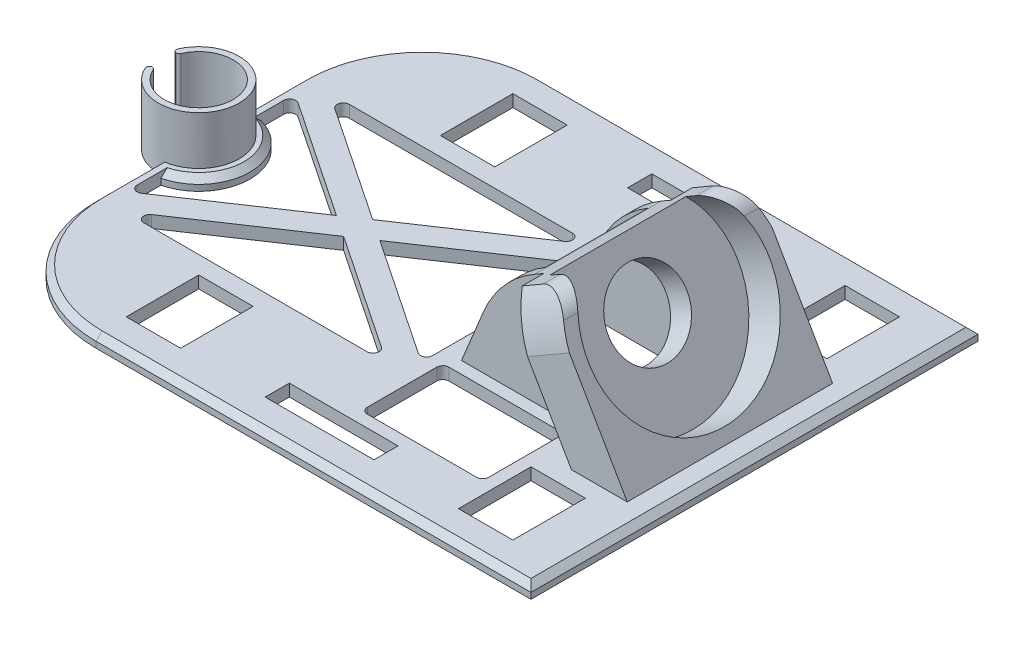
SolidWorks part; units mm, degrees
ref_plane "Plano frontal" through (0, 0, 0) normal (0, 0, 1) x (1, 0, 0)
ref_plane "Plano superior" through (0, 0, 0) normal (0, 1, 0) x (1, 0, 0)
ref_plane "Plano direito" through (0, 0, 0) normal (1, 0, 0) x (0, 0, -1)
sketch "Esboço1" plane through (0, 0, 0) normal (0, 1, 0) x (1, 0, 0)
  line L1 (-23, 18.5) -> (23, 18.5)
  line L2 (-23, 18.5) -> (-23, -18.5)
  line L3 (-23, -18.5) -> (23, -18.5)
  line L4 (23, 18.5) -> (23, -18.5)
  line L5 (-23, 18.5) -> (23, -18.5) construction
  line L6 (-23, -18.5) -> (23, 18.5) construction
  point P0 (0, 0)
  dimension "D1" = 46
  dimension "D2" = 37
extrude "Ressalto-extrusão1" add sketch "Esboço1" along normal blind 1
sketch "Esboço2" plane through (0, 1, 0) normal (0, 1, 0) x (1, 0, 0)
  line L0 (-23, 18.5) -> (-23, -18.5) construction
  line L1 (-13, -16) -> (-8.5, -16)
  line L2 (-13, -16) -> (-13, -10)
  line L3 (-13, -10) -> (-8.5, -10)
  line L4 (-8.5, -16) -> (-8.5, -10)
  line L9 (-1.5, -16) -> (7.5, -16)
  line L10 (-1.5, -16) -> (-1.5, -14)
  line L11 (-1.5, -14) -> (7.5, -14)
  line L12 (7.5, -16) -> (7.5, -14)
  line L13 (14.5, -16) -> (19, -16)
  line L14 (14.5, -16) -> (14.5, -10)
  line L15 (14.5, -10) -> (19, -10)
  line L16 (19, -16) -> (19, -10)
  line L17 (-13, 16) -> (-8.5, 16)
  line L18 (-13, 16) -> (-13, 10)
  line L19 (-13, 10) -> (-8.5, 10)
  line L20 (-8.5, 16) -> (-8.5, 10)
  line L25 (-1.5, 16) -> (7.5, 16)
  line L26 (-1.5, 16) -> (-1.5, 14)
  line L27 (-1.5, 14) -> (7.5, 14)
  line L28 (7.5, 16) -> (7.5, 14)
  line L29 (14.5, 16) -> (19, 16)
  line L30 (14.5, 16) -> (14.5, 10)
  line L31 (14.5, 10) -> (19, 10)
  line L32 (19, 16) -> (19, 10)
  dimension "D1" = 4.5
  dimension "D2" = 10
  dimension "D3" = 28
  dimension "D4" = 14
  dimension "D5" = 2
  dimension "D6" = 2
  dimension "D7" = 6
  dimension "D8" = 6
  dimension "D9" = 7
  dimension "D10" = 9
  dimension "D13" = 7
  dimension "D14" = 4.5
extrude "Corte-extrusão1" cut sketch "Esboço2" against normal blind 3
sketch "Esboço3" plane through (0, 1, 0) normal (0, 1, 0) x (1, 0, 0)
  line L0 (23, -18.5) -> (23, 18.5) construction
  line L1 (4, 8.4674) -> (21, 8.4674)
  line L2 (4, 8.4674) -> (4, -8.5326)
  line L3 (4, -8.5326) -> (21, -8.5326)
  line L4 (21, 8.4674) -> (21, -8.5326)
  line L5 (4, 8.4674) -> (21, -8.5326) construction
  line L6 (4, -8.5326) -> (21, 8.4674) construction
  point P0 (12.5, -0.0326)
  dimension "D1" = 17
  dimension "D2" = 17
  dimension "D3" = 2
extrude "Ressalto-extrusão2" add sketch "Esboço3" along normal blind 15
chamfer "Chanfro1" distance 15 angle 30 1 edges at (21, 16, 0.0326) first distance on face at (21, 8.5, 0.0326)
sketch "Esboço4" plane through (16.183, 9.3433, 0) normal (0.866, 0.5, 0) x (0, 0, -1)
  line L0 (-8.5326, -9.634) -> (8.4674, -9.634) construction
  circle A0 centre (0, -1.134) radius 7.5
  dimension "D1" = 15
  dimension "D2" = 8.5
extrude "Corte-extrusão2" cut sketch "Esboço4" against normal blind 3
sketch "Esboço5" plane through (13.5849, 7.8433, 0) normal (0.866, 0.5, 0) x (0, 0, -1)
  circle A0 centre (0, -1.134) radius 3.25
  dimension "D1" = 6.5
extrude "Corte-extrusão3" cut sketch "Esboço5" against normal blind 2
sketch "Esboço6" plane through (11.8529, 6.8433, 0) normal (0.866, 0.5, 0) x (0, 0, -1)
  line L1 (-4.25, 5.167) -> (4.25, 5.167)
  line L2 (-4.25, 5.167) -> (-4.25, -7.4349)
  line L3 (-4.25, -7.4349) -> (4.25, -7.4349)
  line L4 (4.25, 5.167) -> (4.25, -7.4349)
  line L5 (-4.25, 5.167) -> (4.25, -7.4349) construction
  line L6 (-4.25, -7.4349) -> (4.25, 5.167) construction
  point P0 (0, -1.134)
  dimension "D1" = 8.5
extrude "Corte-extrusão4" cut sketch "Esboço6" against normal blind 10
sketch "Esboço7" plane through (16.183, 9.3433, 0) normal (0.866, 0.5, 0) x (0, 0, -1)
  line L1 (-8.5326, 7.6865) -> (8.4674, 7.6865)
  line L2 (-8.5326, 7.6865) -> (-8.5326, 11.8564)
  line L3 (-8.5326, 11.8564) -> (8.4674, 11.8564)
  line L4 (8.4674, 7.6865) -> (8.4674, 11.8564)
extrude "Corte-extrusão5" cut sketch "Esboço7" against normal blind 10
sketch "Esboço10" plane through (-2.5835, 4.4747, 0) normal (0.5, -0.866, 0) x (0.866, 0.5, 0)
  line L1 (7.602, 4.25) -> (13.6865, 4.25)
  line L2 (7.602, 4.25) -> (7.602, -4.25)
  line L3 (7.602, -4.25) -> (13.6865, -4.25)
  line L4 (13.6865, 4.25) -> (13.6865, -4.25)
extrude "Corte-extrusão6" cut sketch "Esboço10" along normal blind 20
sketch "Esboço11" plane through (4, 0, 0) normal (-1, 0, 0) x (0, 0, 1)
  line L1 (-4.25, 11.318) -> (4.25, 11.318)
  line L2 (-4.25, 11.318) -> (-4.25, 8.2757)
  line L3 (-4.25, 8.2757) -> (4.25, 8.2757)
  line L4 (4.25, 11.318) -> (4.25, 8.2757)
extrude "Corte-extrusão7" cut sketch "Esboço11" against normal up to surface (5.2694 mm away) up to face at (12.5366, 5.659, 0)
sketch "Esboço12" plane through (-3.8433, 6.6567, 0) normal (-0.5, 0.866, 0) x (0.866, 0.5, 0)
  line L1 (13.6865, -4.25) -> (9.3225, -4.25)
  line L2 (13.6865, -4.25) -> (13.6865, 4.25)
  line L3 (13.6865, 4.25) -> (9.3225, 4.25)
  line L4 (9.3225, -4.25) -> (9.3225, 4.25)
extrude "Corte-extrusão8" cut sketch "Esboço12" against normal blind 8
sketch "Esboço17" plane through (0, 1, 0) normal (0, 1, 0) x (1, 0, 0)
  line L0 (-23, 18.5) -> (-23, -18.5) construction
  circle A0 centre (-23, 0) radius 3.35
  dimension "D1" = 6.7
extrude "Ressalto-extrusão4" add sketch "Esboço17" along normal blind 5 from offset 1 offset against normal yes
sketch "Esboço18" plane through (0, 5, 0) normal (0, 1, 0) x (1, 0, 0)
  circle A0 centre (-23, 0) radius 2.85
  dimension "D1" = 5.7
extrude "Corte-extrusão11" cut sketch "Esboço18" against normal blind 10
sketch "Esboço19" plane through (-23, 0, 0) normal (-1, 0, 0) x (0, 0, 1)
  line L0 (-0.988, 10.7689) -> (-0.988, -0.812)
  line L1 (-0.988, 10.7689) -> (1.012, 10.7689)
  line L2 (-0.988, -0.812) -> (1.012, -0.812)
  line L3 (1.012, 10.7689) -> (1.012, -0.812)
  line L4 (-0.988, 10.7689) -> (1.012, -0.812) construction
  line L5 (-0.988, -0.812) -> (1.012, 10.7689) construction
  point P0 (-0.988, -0.812)
  point P1 (0.012, 4.9785)
  dimension "D1" = 2
extrude "Corte-extrusão12" cut sketch "Esboço19" along normal blind 6
sketch "Esboço25" plane through (16.183, 9.3433, 0) normal (0.866, 0.5, 0) x (0, 0, -1)
  line L0 (-8.6, -1.134) -> (-8.6651, 8.1195)
  line L1 (-8.6651, 8.1195) -> (8.6, 8.1195)
  line L2 (8.6, 8.1195) -> (8.6, -1.134)
  arc A0 (8.6, -1.134) -> (-8.6, -1.134) centre (0, -1.134) ccw
  dimension "D1" = 8.6
extrude "Corte-extrusão17" cut sketch "Esboço25" against normal up to surface (14.7224 mm away) up to face at (8.1699, 1, 0.0163)
sketch "Esboço26" plane through (0, 0, 8.5326) normal (0, 0, 1) x (1, 0, 0)
  line L0 (4, 1) -> (8.6816, 12.336)
  line L1 (8.6816, 12.336) -> (1.8349, 10.7026)
  line L2 (1.8349, 10.7026) -> (4, 1)
extrude "Corte-extrusão18" cut sketch "Esboço26" against normal blind 34
ref_plane "Plano1" through (-3.1712, 5.4928, 0) normal (0.5, -0.866, 0) x (-0.866, -0.5, 0)
sketch "Esboço28" plane through (-3.1712, 5.4928, 0) normal (0.5, -0.866, 0) x (-0.866, -0.5, 0)
  line L0 (-14.6865, -8.5326) -> (-14.6865, -5.25)
  line L1 (-18.6865, -8.5326) -> (-5.3618, -8.5326) construction
  line L2 (-14.6865, -5.25) -> (-3.9641, -5.25)
  line L3 (-3.9641, -4.25) -> (-3.9641, -8.5326) construction
  line L4 (-3.9641, -5.25) -> (-3.9641, -8.5326)
  line L5 (-3.9641, -8.5326) -> (-14.6865, -8.5326)
  line L6 (-14.6865, 8.4674) -> (-14.6865, 5.25)
  line L7 (-5.9202, 8.4674) -> (-18.6865, 8.4674) construction
  line L8 (-14.6865, 5.25) -> (-3.9641, 5.25)
  line L9 (-3.9641, 8.4674) -> (-3.9641, 4.25) construction
  line L10 (-3.9641, 5.25) -> (-3.9641, 8.4674)
  line L11 (-3.9641, 8.4674) -> (-14.6865, 8.4674)
  line L12 (-13.6865, 4.25) -> (-3.9641, 4.25) construction
  line L13 (-3.9641, -4.25) -> (-13.6865, -4.25) construction
  line L14 (-15.6865, 7.5) -> (-15.6865, -7.5) construction
  dimension "D1" = 1
  dimension "D2" = 1
  dimension "D3" = 1
extrude "Corte-extrusão20" cut sketch "Esboço28" along normal up to surface (7.4765 mm away) up to face at (3, 1, -15)
sketch "Esboço30" plane through (0, 1, 0) normal (0, 1, 0) x (1, 0, 0)
  line L0 (3.327, -8.5326) -> (4, -8.5326) construction
  line L1 (2.4553, 8.4674) -> (-22, 8.4674)
  line L2 (2.4553, 8.4674) -> (2.4553, -8.5326)
  line L3 (2.4553, -8.5326) -> (-22, -8.5326)
  line L4 (-22, 8.4674) -> (-22, 4.1307)
  line L5 (3.0581, 8.4674) -> (4, 8.4674) construction
  line L6 (-23, 18.5) -> (-23, 3.35) construction
  line L7 (-22, -4.1307) -> (-22, -8.5326)
  arc A0 (-22, -4.1307) -> (-22, 4.1307) centre (-23, 0) ccw
  dimension "D2" = 8.5
  dimension "D1" = 1
extrude "Corte-extrusão21" cut sketch "Esboço30" against normal blind 10
sketch "Esboço31" plane through (0, 1, 0) normal (0, 1, 0) x (1, 0, 0)
  line L0 (-20.65, -8.5326) -> (-9.7723, -1.2367)
  line L1 (-22, -8.5326) -> (2.4553, -8.5326) construction
  line L2 (2.4553, -8.5326) -> (2.4553, 8.4674) construction
  line L3 (2.4553, 6.9647) -> (2.4553, 8.4674)
  line L4 (2.4553, 8.4674) -> (1.1053, 8.4674)
  line L5 (2.4553, 8.4674) -> (-22, 8.4674) construction
  line L6 (1.1053, 8.4674) -> (-9.7723, 1.1715)
  line L7 (-22, -4.1307) -> (-22, -8.5326) construction
  line L8 (-22, -7.0298) -> (-22, -8.5326)
  line L9 (-22, -8.5326) -> (-20.65, -8.5326)
  line L10 (2.4553, -7.0298) -> (-7.9771, -0.0326)
  line L11 (-20.65, 8.4674) -> (-22, 8.4674)
  line L12 (-22, 8.4674) -> (-22, 4.1307) construction
  line L13 (-22, 6.9647) -> (-11.5676, -0.0326)
  line L14 (1.1053, -8.5326) -> (2.4553, -8.5326)
  line L15 (2.4553, -8.5326) -> (2.4553, -7.0298)
  line L16 (-22, 8.4674) -> (-22, 6.9647)
  line L17 (-11.5676, -0.0326) -> (-22, -7.0298)
  line L18 (-9.7723, -1.2367) -> (1.1053, -8.5326)
  line L19 (-9.7723, 1.1715) -> (-20.65, 8.4674)
  line L20 (-7.9771, -0.0326) -> (2.4553, 6.9647)
  dimension "D1" = 2
  dimension "D2" = 2
  dimension "D3" = 1.35
  dimension "D4" = 1.35
  dimension "D5" = 1.35
extrude "Ressalto-extrusão5" add sketch "Esboço31" against normal blind 1
fillet "Filete2" radius 10 2 edges at (-23, 0.5, 18.5) (-23, 0.5, -18.5)
sketch "Esboço33" plane through (16.183, 9.3433, 0) normal (0.866, 0.5, 0) x (0, 0, -1)
  line L1 (-8.9097, 11.1219) -> (8.9097, 11.1219)
  line L2 (-8.9097, 11.1219) -> (-8.9097, 3.8101)
  line L3 (-8.9097, 3.8101) -> (8.9097, 3.8101)
  line L4 (8.9097, 11.1219) -> (8.9097, 3.8101)
  line L5 (-8.9097, 11.1219) -> (8.9097, 3.8101) construction
  line L6 (-8.9097, 3.8101) -> (8.9097, 11.1219) construction
  arc A0 (8.4674, 0.3702) -> (-8.5326, -0.0591) centre (0, -1.134) ccw construction
  point P0 (0, 7.466)
extrude "Corte-extrusão23" cut sketch "Esboço33" against normal blind 13.5
fillet "Filete3" radius 10 1 edges at (7.0959, 8.4964, 4.75)
fillet "Filete4" radius 2 2 edges at (14.2779, 12.643, 6.3382) (14.2779, 12.643, -6.3382)
chamfer "Chanfro3" distance 0.5 angle 45 8 edges at (-18.75, 1, 0) (-23, 1, -5.925) (-23, 1, 5.925) (-20.0711, 1, -15.5711) (-20.0711, 1, 15.5711) (5, 1, -18.5) (5, 1, 18.5) (23, 1, 0)
sketch "Esboço34" plane through (0, 1, 0) normal (0, 1, 0) x (1, 0, 0)
  line L0 (-1.5, 14) -> (7.5, 14) construction
  line L1 (3.4553, -6.25) -> (13.5, -6.25)
  line L2 (3.4553, -6.25) -> (3.4553, -13)
  line L3 (3.4553, -13) -> (13.5, -13)
  line L4 (13.5, -6.25) -> (13.5, -13)
  line L5 (3.4553, -6.25) -> (13.5, -13) construction
  line L6 (3.4553, -13) -> (13.5, -6.25) construction
  line L7 (3.4553, 13.2417) -> (13.5, 13.2417)
  line L8 (3.4553, 13.2417) -> (3.4553, 6.25)
  line L9 (3.4553, 6.25) -> (13.5, 6.25)
  line L10 (13.5, 13.2417) -> (13.5, 6.25)
  line L11 (3.4553, 13.2417) -> (13.5, 6.25) construction
  line L12 (3.4553, 6.25) -> (13.5, 13.2417) construction
  line L13 (4, 5.25) -> (16.3812, 5.25) construction
  line L14 (16.3812, -5.25) -> (4, -5.25) construction
  line L15 (2.4553, -7.0298) -> (2.4553, 6.9647) construction
  line L16 (14.5, -10) -> (14.5, -16) construction
  line L17 (7.5, -14) -> (-1.5, -14) construction
  line L18 (14.5, 16) -> (14.5, 10) construction
  point P0 (8.4777, -9.625)
  point P5 (8.4777, 9.7459)
  dimension "D1" = 0.7583
  dimension "D2" = 1
  dimension "D3" = 1
  dimension "D4" = 1
  dimension "D5" = 1
  dimension "D6" = 1
  dimension "D7" = 1
  dimension "D8" = 1
extrude "Corte-extrusão24" cut sketch "Esboço34" against normal blind 13.5
fillet "Filete5" radius 0.5 16 edges at (13.5, 0.5, -13.2417) (3.4553, 0.5, -13.2417) (3.4553, 0.5, -6.25) (13.5, 0.5, -6.25) (13.5, 0.5, 13) (3.4553, 0.5, 13) (13.5, 0.5, 6.25) (3.4553, 0.5, 6.25) (-22, 0.5, 7.0298) (-22, 0.5, -6.9647) (1.1053, 0.5, -8.4674) (2.4553, 0.5, -6.9647) (-20.65, 0.5, -8.4674) (-20.65, 0.5, 8.5326) (1.1053, 0.5, 8.5326) (2.4553, 0.5, 7.0298)
fillet "Filete6" radius 0.25 4 edges at (-25.6733, 2.5, -0.988) (-26.201, 2.5, -0.988) (-25.6643, 2.5, 1.012) (-26.1935, 2.5, 1.012)
